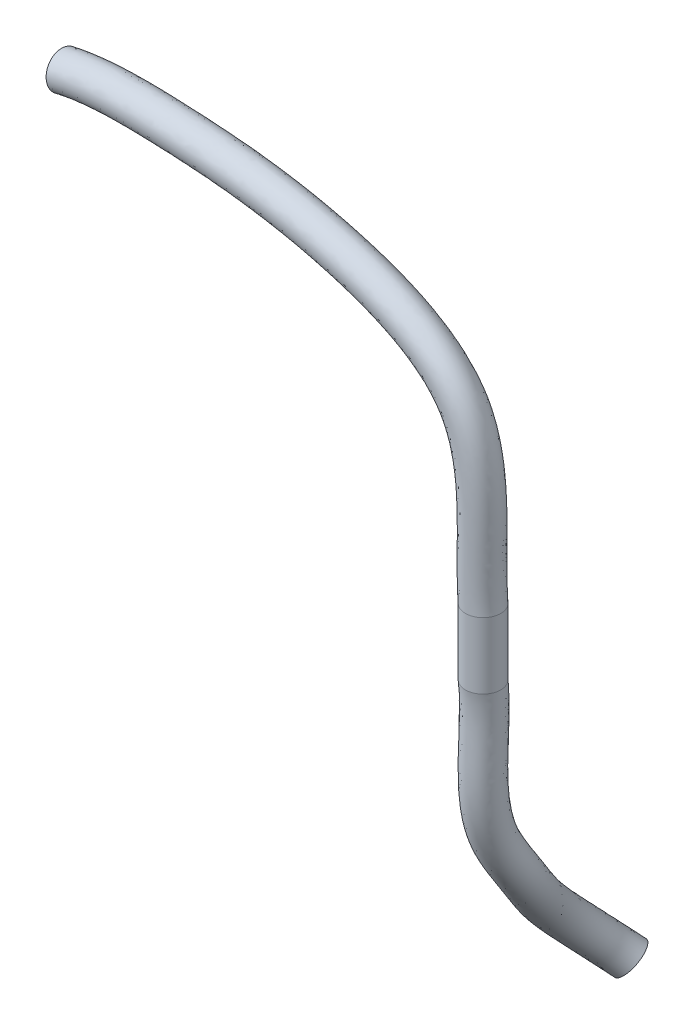
SolidWorks part; units mm, degrees
ref_plane "Front Plane" through (0, 0, 0) normal (0, 0, 1) x (1, 0, 0)
ref_plane "Top Plane" through (0, 0, 0) normal (0, 1, 0) x (1, 0, 0)
ref_plane "Right Plane" through (0, 0, 0) normal (1, 0, 0) x (0, 0, -1)
sketch "Sketch1" plane through (0, 0, 0) normal (0, 1, 0) x (1, 0, 0)
  circle A0 centre (0, 0) radius 4
  circle A1 centre (0, 0) radius 3
extrude "Boss-Extrude1" add sketch "Sketch1" along normal blind 15
sketch3d "3DSketch1"
  spline S0 degree 3 poles (0, 0, 0) (-0.0962, -8.7197, -0.9781) (0.1087, -20.2715, 1.5978) (-0.0858, -33.669, -2.8985) (1.5667, -52.3543, -14.4212) (-16.505, -64.4309, -27.8847) (-5.5142, -76.8386, -38.9233) knots 0 0 0 0 0.292865 0.357985 0.457145 1 1 1 1
sweep "Sweep1" add profiles "Sketch1<4>" path "3DSketch1"
sketch "Sketch1<4>" plane through (0, 0, 0) normal (0, 1, 0) x (1, 0, 0) same geometry as "Sketch1"
sketch "Sketch3" plane through (0, 15, 0) normal (0, 1, 0) x (1, 0, 0)
  circle A0 centre (0, 0) radius 3
  circle A1 centre (0, 0) radius 4
sketch3d "3DSketch2"
  spline S0 degree 3 poles (0, 15, 0) (-0.9587, 26.1757, 0) (3.8391, 54.531, 0) (-34.963, 70.8676, 0) (-65.5121, 73.7697, 0) (-87.3606, 73.9116, 0) (-94.9904, 72.1946, 0) knots 0 0 0 0 0.278374 0.513699 0.823618 1 1 1 1
sweep "Sweep2" add profiles "Sketch3" path "3DSketch2"
